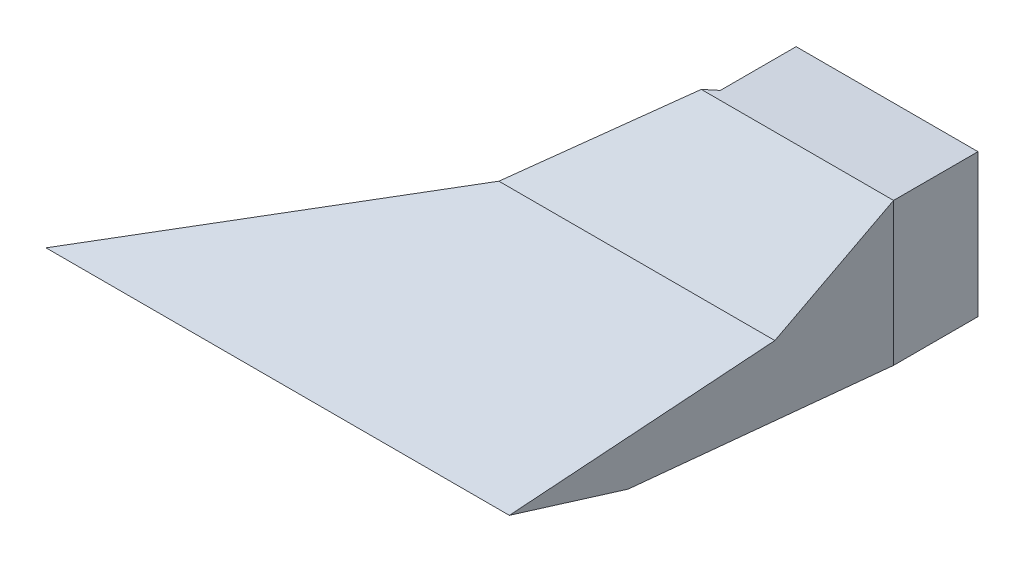
SolidWorks part; units mm, degrees
ref_plane "Front"
ref_plane "Top" through (0, 0, 0) normal (0, 1, 0) x (1, 0, 0)
ref_plane "Right" through (0, 0, 0) normal (1, 0, 0) x (0, 0, -1)
sketch "Side base sketch" plane through (0, 0, 0) normal (-1, 0, 0) x (0, 0, 1)
  line L0 (0, 13.2) -> (8.4913, 5)
  line L1 (0, 0) -> (6, -1)
  line L2 (6, -1) -> (19, -3.1667)
  line L3 (8.4913, 5) -> (19.4913, 0.803)
  line L4 (19.4913, 0.803) -> (27.4913, -2.2493)
  line L5 (27.4913, -2.2493) -> (19, -3.1667)
  line L6 (0, 13.2) -> (0, 0)
  dimension "D1" = 6
  dimension "D2" = 6
  dimension "D3" = 1
  dimension "D4" = 46
  dimension "D5" = 13
  dimension "D6" = 11
  dimension "D7" = 4
  dimension "D8" = 8
  dimension "D9" = 13.2
extrude "Side base" add sketch "Side base sketch" against normal blind 0.8
pattern_linear "Side base 2" count 2 spacing 50 along (1, 0, 0) of bodies 108
sketch "Wall base sketch" plane through (0.8, 0, 0) normal (1, 0, 0) x (0, 0, -1)
  line L0 (0, 12.0879) -> (-8.0533, 4.3109)
  line L1 (-8.0533, 4.3109) -> (-25.7424, -2.4382)
  line L3 (-19, -3.4019) -> (-19, 4.6777) construction
  line L4 (0, 13.2) -> (0, 0) construction
  line L5 (0, 0) -> (-19, -3.1667) construction
  line L8 (-8.4913, 5) -> (0, 13.2) construction
  line L9 (0, 0.811) -> (-19, -2.3556)
  line L11 (-19, -2.3556) -> (-19, -3.1667)
  line L12 (-19, -3.1667) -> (0, 0)
  line L13 (0, 0) -> (0, 0.811)
  line L14 (-25.7424, -2.4382) -> (-27.4913, -2.2493)
  line L15 (-27.4913, -2.2493) -> (-8.4913, 5)
  line L16 (-8.4913, 5) -> (0, 13.2)
  line L17 (0, 13.2) -> (0, 12.0879)
  line L18 (-19, -3.1667) -> (-27.4913, -2.2493) construction
  dimension "D1" = 0.8
  dimension "D2" = 0.8
  dimension "D3" = 0.8
extrude "Front back walls" add sketch "Wall base sketch" along normal up to next
sketch "Base sketch" plane through (0, 0, 0) normal (0, 0, -1) x (-1, 0, 0)
  line L0 (-50, 12.0879) -> (-0.8, 12.0879) construction
  line L1 (0, 13.2) -> (-50.8, 13.2)
  line L2 (0, 13.2) -> (0, 0)
  line L3 (0, 0) -> (-50.8, 0)
  line L4 (-50.8, 13.2) -> (-50.8, 0)
  line L5 (-50, 0.811) -> (-34.8, 0.811)
  line L6 (-50, 0.811) -> (-50, 12.0879)
  line L7 (-50, 12.0879) -> (-34.8, 12.0879)
  line L8 (-34.8, 0.811) -> (-34.8, 12.0879)
  dimension "D1" = 15.2
extrude "Base" add sketch "Base sketch" along normal blind 0.8
sketch "Attachment base sketch" plane through (0, 0, -0.8) normal (0, 0, -1) x (-1, 0, 0)
  line L0 (-50.8, 0) -> (0, 0) construction
  line L1 (-50.8, 13.2) -> (-34, 13.2)
  line L2 (-50.8, 13.2) -> (-50.8, 0)
  line L3 (-50.8, 0) -> (-34, 0)
  line L4 (-34, 13.2) -> (-34, 0)
  line L5 (-34.8, 0.811) -> (-34.8, 12.0879) construction
  line L7 (-34.8, 12.0879) -> (-50, 12.0879)
  line L8 (-34.8, 12.0879) -> (-34.8, 0.811)
  line L9 (-34.8, 0.811) -> (-50, 0.811)
  line L10 (-50, 12.0879) -> (-50, 0.811)
  dimension "D1" = 0.8
extrude "Attachment base" add sketch "Attachment base sketch" along normal blind 7
sketch "Sketch1" plane through (0, 0, -7.8) normal (0, 0, -1) x (-1, 0, 0)
  line L1 (-50, 12.0879) -> (-34.8, 12.0879)
  line L2 (-50, 12.0879) -> (-50, 0.811)
  line L3 (-50, 0.811) -> (-34.8, 0.811)
  line L4 (-34.8, 12.0879) -> (-34.8, 0.811)
extrude "Fan base" add sketch "Sketch1" along normal blind 0.1 separate body
sketch "Sketch4" plane through (0.8, 0, 0) normal (1, 0, 0) x (0, 0, -1)
  line L0 (-25.7424, -2.4382) -> (-19, -3.1667)
  line L1 (-19, -3.1667) -> (-19, -2.3556)
  line L2 (-19, -2.3556) -> (0, 0.811)
  line L3 (0, 0.811) -> (0, 12.0879)
  line L4 (-8.0533, 4.3109) -> (0, 12.0879) construction
  line L5 (0, 12.0879) -> (0, 0.811) construction
  line L6 (0, 12.0879) -> (-8.0533, 4.3109)
  line L7 (-8.0533, 4.3109) -> (-25.7424, -2.4382)
extrude "Left right wall removal" cut sketch "Sketch4" against normal through all both and the other way through all
ref_point "Cutaway left intersection point" parameters "D1"=8
ref_plane "Cutaway left plane" through (46.834, 0, 13.6287) normal (0.9602, 0, 0.2794) x (0.2794, 0, -0.9602)
sketch "Sketch6" plane through (46.834, 0, 13.6287) normal (0.9602, 0, 0.2794) x (0.2794, 0, -0.9602)
  line L1 (-14.4376, -3.1667) -> (14.1941, -3.1667)
  line L2 (-14.4376, -3.1667) -> (-14.4376, 13.2)
  line L3 (-14.4376, 13.2) -> (14.1941, 13.2)
  line L4 (14.1941, -3.1667) -> (14.1941, 13.2)
  point P4 (-14.4376, -2.2493)
  point P6 (-5.5941, -3.1667)
extrude "Cutaway left" cut sketch "Sketch6" along normal through all
sketch "Sketch7" plane through (46.834, 0, 13.6287) normal (0.9602, 0, 0.2794) x (0.2794, 0, -0.9602)
  line L0 (-5.5941, -2.3556) -> (-5.5941, -3.1667)
  line L1 (-5.5941, -3.1667) -> (-12.6161, -2.4382)
  line L2 (-12.6161, -2.4382) -> (5.8067, 4.3109)
  line L3 (5.8067, 4.3109) -> (14.1941, 12.0879)
  line L4 (14.1941, 12.0879) -> (14.1941, 0.811)
  line L5 (14.1941, 0.811) -> (-5.5941, -2.3556)
extrude "Left wall" add sketch "Sketch7" along direction (-1, 0, 0) on the side against the normal blind 0.8332
ref_point "Cutaway right intersection point 1" parameters "D1"=4
ref_point "Cutaway right intersection point 2" parameters "D1"=4
ref_plane "Cutaway right plane" through (13.5167, 0, 16.2441) normal (0.6396, 0, 0.7687) x (0.7687, 0, -0.6396)
sketch "Sketch9" plane through (13.5167, 0, 16.2441) normal (0.6396, 0, 0.7687) x (0.7687, 0, -0.6396)
  line L1 (26.6471, 13.2) -> (-17.5841, 13.2)
  line L2 (26.6471, 13.2) -> (26.6471, -3.1667)
  line L3 (26.6471, -3.1667) -> (-17.5841, -3.1667)
  line L4 (-17.5841, 13.2) -> (-17.5841, -3.1667)
extrude "Cutaway right" cut sketch "Sketch9" against normal through all
sketch "Sketch10" plane through (13.5167, 0, 16.2441) normal (-0.6396, 0, -0.7687) x (-0.7687, 0, 0.6396)
  line L0 (-25.3964, 12.0879) -> (-25.3964, 0.811)
  line L1 (-25.3964, 0.811) -> (4.3086, -2.3556)
  line L2 (4.3086, -2.3556) -> (4.3086, -3.1667)
  line L3 (4.3086, -3.1667) -> (14.8498, -2.4382)
  line L4 (14.8498, -2.4382) -> (-12.8057, 4.3109)
  line L5 (-12.8057, 4.3109) -> (-25.3964, 12.0879)
extrude "Right wall" add sketch "Sketch10" along direction (-1, 0, 0) on the side against the normal blind 1.2507
sketch "Sketch11" plane through (0, 0, -7.8) normal (0, 0, -1) x (-1, 0, 0)
  line L0 (-34, 13.2) -> (-50.8, 13.2) construction
  line L1 (-50, 12.0879) -> (-34.8, 12.0879)
  line L2 (-50, 12.0879) -> (-50, 12.4)
  line L3 (-50, 12.4) -> (-34.8, 12.4)
  line L4 (-34.8, 12.0879) -> (-34.8, 12.4)
  dimension "D1" = 0.8
extrude "Pipe top extra cutaway" cut sketch "Sketch11" against normal up to surface (7.8 mm away) up to face at (42.1271, 8.9771, 3.2213)
ref_plane "Air flow cut plane" through (0, 0, 27.4913) normal (0, 0, 1) x (1, 0, 0)
equation "\"wall_thicknes\" = 0.8"
equation "\"D1@Base\" = \"wall_thicknes\""
equation "\"D1@Wall base sketch\"=\"wall_thicknes\""
equation "\"D1@Side base\"=\"wall_thicknes\""
equation "\"D2@Wall base sketch\"=\"wall_thicknes\""
equation "\"D3@Wall base sketch\"=\"wall_thicknes\""
equation "\"D1@Base sketch\"=\"wall_thicknes\"*-2+16.8"
equation "\"D1@Attachment base sketch\"=\"wall_thicknes\""
equation "\"D1@Left wall\"=\"left_wall_thickness\""
equation "\"D1@Sketch11\"=\"wall_thicknes\""
equation "\"left_wall_thickness\" = 0.83318430202930948562"
equation "\"right_wall_thickness\" = 1.25073472653581935106"
equation "\"D1@Right wall\"=\"right_wall_thickness\""
